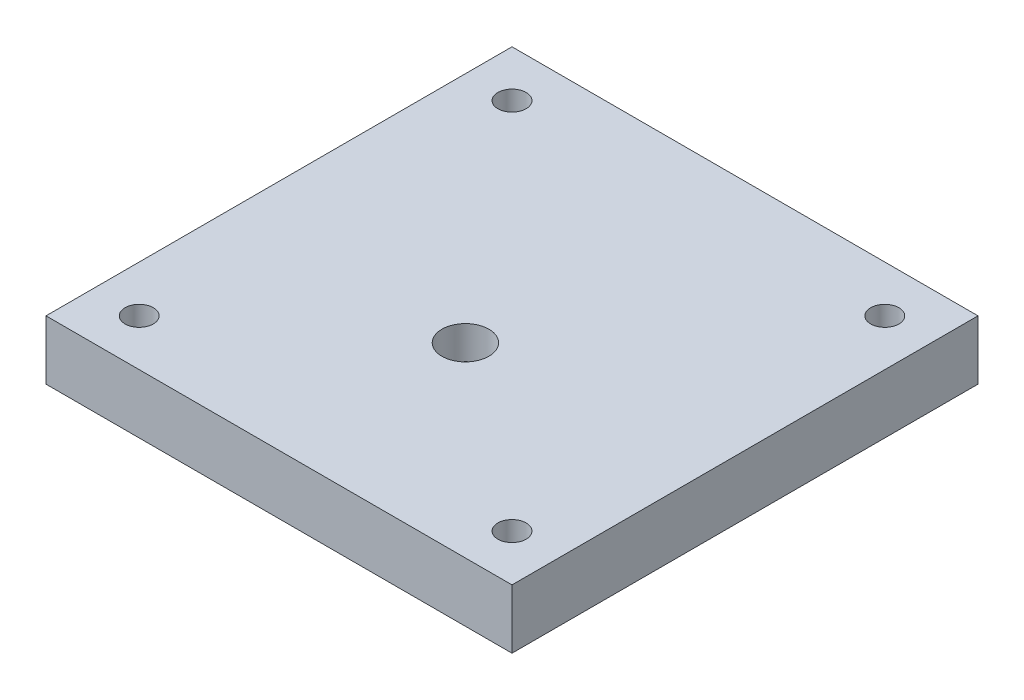
SolidWorks part; units mm, degrees
ref_plane "Front Plane" through (0, 0, 0) normal (0, 0, 1) x (1, 0, 0)
ref_plane "Top Plane" through (0, 0, 0) normal (0, 1, 0) x (1, 0, 0)
ref_plane "Right Plane" through (0, 0, 0) normal (1, 0, 0) x (0, 0, -1)
sketch "Sketch1" plane through (0, 0, 0) normal (0, 1, 0) x (1, 0, 0)
  line L1 (-50, 60) -> (50, 60)
  line L2 (-50, 60) -> (-50, -40)
  line L3 (-50, -40) -> (50, -40)
  line L4 (50, 60) -> (50, -40)
  point P0 (0, 0)
  point P8 (0, -40)
  dimension "D1" = 100
  dimension "D2" = 100
  dimension "D3" = 40
extrude "Boss-Extrude1" add sketch "Sketch1" along normal blind 12.7 contours L4 L3 L2 L1
hole_wizard "M5 Clearance Hole1" positions "Sketch2" profile "Sketch3" hole size "M5" standard "ANSI Metric" end condition through all
sketch "Sketch2" plane through (0, 12.7, 0) normal (0, 1, 0) x (1, 0, 0)
  line L3 (-40, -30) -> (40, -30)
  line L4 (-40, -30) -> (-40, 50)
  line L5 (-40, 50) -> (40, 50)
  line L6 (40, -30) -> (40, 50)
  line L7 (-40, -30) -> (40, 50) construction
  line L8 (-40, 50) -> (40, -30) construction
  point P0 (-40, 50)
  point P2 (40, 50)
  point P4 (40, -30)
  point P6 (-40, -30)
  point P123 (0, 10)
  dimension "D1" = 80
  dimension "D2" = 80
  dimension "D3" = 10
sketch "Sketch3" plane through (-40, 12.7, -50) normal (1, 0, 0) x (0, 0, 1)
  line L0 (0, 0) -> (0, 12.7)
  line L1 (0, 12.7) -> (3.03, 12.7)
  line L2 (3.03, 12.7) -> (3.03, 0)
  line L5 (3.03, 0) -> (0, 0)
  line L11 (0, -6.35) -> (0, 107.95) construction
  dimension "Thru Hole Dia." = 6.06
  dimension "Thru Hole Depth" = 12.7
hole_wizard "CSK for 3/8 Flat Head Socket Cap Screw1" positions "Sketch4" profile "Sketch5" countersink size "3/8" standard "ANSI Inch" end condition through all
sketch "Sketch4" plane through (0, 0, 0) normal (0, -1, 0) x (-1, 0, 0)
  point P0 (0, 0)
sketch "Sketch5" plane through (0, 0, 0) normal (1, 0, 0) x (0, 0, -1)
  line L0 (0, 0) -> (0, 12.7)
  line L1 (0, 12.7) -> (5.0419, 12.7)
  line L2 (5.0419, 12.7) -> (5.0419, 5.6101)
  line L3 (5.0419, 5.6101) -> (9.9187, 0)
  line L5 (9.9187, 0) -> (0, 0)
  line L6 (-5.0419, 5.6101) -> (-9.9187, 0) construction
  line L11 (0, -6.35) -> (0, 107.95) construction
  dimension "Thru Hole Dia." = 10.0838
  dimension "Thru Hole Depth" = 12.7
  dimension "Near C'Sink Dia." = 19.8374
  dimension "Near C'Sink Angle" = 82
ref_axis "Axis1" through (0, 12.7, 0) along (0, -1, 0)
